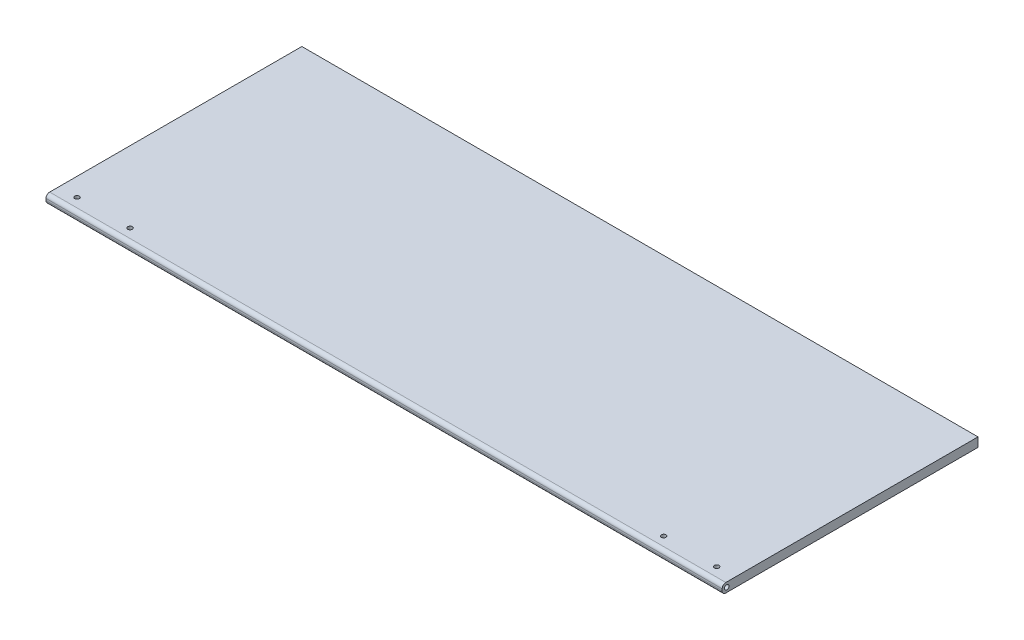
SolidWorks part; units mm, degrees
material "6061 Alloy"
ref_plane "Front Plane" through (0, 0, 0) normal (0, 0, 1) x (1, 0, 0)
ref_plane "Top Plane" through (0, 0, 0) normal (0, 1, 0) x (1, 0, 0)
ref_plane "Right Plane" through (0, 0, 0) normal (1, 0, 0) x (0, 0, -1)
sketch "Sketch1" plane through (0, 0, 0) normal (0, 1, 0) x (1, 0, 0)
  line L1 (-234.95, 88.9) -> (234.95, 88.9)
  line L2 (-234.95, 88.9) -> (-234.95, -88.9)
  line L3 (-234.95, -88.9) -> (234.95, -88.9)
  line L4 (234.95, 88.9) -> (234.95, -88.9)
  line L5 (-234.95, 88.9) -> (234.95, -88.9) construction
  line L6 (-234.95, -88.9) -> (234.95, 88.9) construction
  point P0 (0, 0)
  dimension "D1" = 177.8
  dimension "D2" = 469.9
extrude "Boss-Extrude1" add sketch "Sketch1" along normal blind 6.35
sketch "Sketch2" plane through (-234.95, 0, 0) normal (-1, 0, 0) x (0, 0, 1)
  line L0 (-88.9, 6.35) -> (88.9, 6.35) construction
  line L1 (88.9, 6.35) -> (88.9, 0) construction
  circle A0 centre (85.725, 3.175) radius 1.5875
  dimension "D1" = 3.175
  dimension "D2" = 3.175
  dimension "D3" = 3.175
extrude "Cut-Extrude1" cut sketch "Sketch2" against normal through all
fillet "Fillet1" radius 2.54 2 edges at (0, 0, 88.9) (0, 6.35, 88.9)
sketch "Sketch3" plane through (234.95, 0, 0) normal (1, 0, 0) x (0, 0, -1)
  line L0 (88.9, 6.35) -> (88.9, 0) construction
  line L1 (-48.26, 4.572) -> (-33.02, 4.572)
  line L2 (-48.26, 4.572) -> (-48.26, 1.27)
  line L3 (-48.26, 1.27) -> (-33.02, 1.27)
  line L4 (-33.02, 4.572) -> (-33.02, 1.27)
  line L5 (-48.26, 4.572) -> (-33.02, 1.27) construction
  line L6 (-48.26, 1.27) -> (-33.02, 4.572) construction
  line L7 (-86.36, 0) -> (88.9, 0) construction
  point P0 (-40.64, 2.921)
  dimension "D1" = 15.24
  dimension "D2" = 129.54
  dimension "D3" = 3.302
  dimension "D4" = 1.27
sketch "Sketch4" plane through (0, 0, 0) normal (0, -1, 0) x (1, 0, 0)
  line L0 (234.95, 86.36) -> (-234.95, 86.36) construction
  line L1 (-234.95, -88.9) -> (-234.95, 86.36) construction
  circle A0 centre (-185.42, 80.01) radius 1.5875
  circle A1 centre (-222.25, 80.01) radius 1.5875
  dimension "D2" = 3.175
  dimension "D1" = 6.35
  dimension "D3" = 36.83
  dimension "D4" = 12.7
extrude "Cut-Extrude3" cut sketch "Sketch4" against normal through all
mirror "Mirror1" about plane through (0, 0, 0) normal (1, 0, 0) of "Cut-Extrude3"
